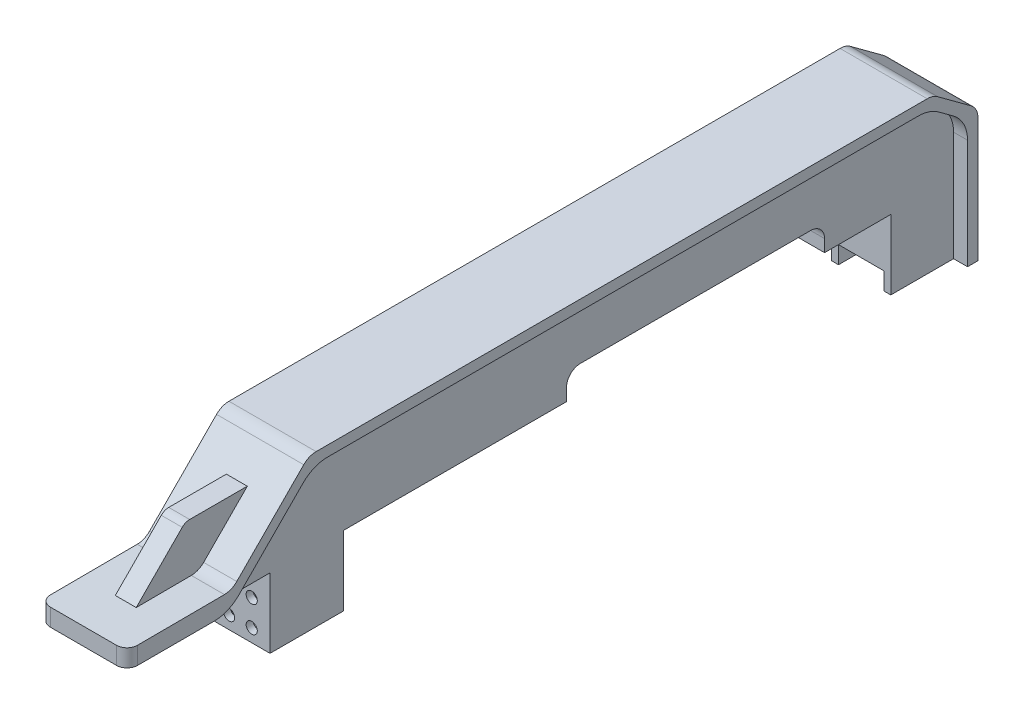
SolidWorks part; units mm, degrees
ref_plane "Front Plane" through (0, 0, 0) normal (0, 0, 1) x (1, 0, 0)
ref_plane "Top Plane" through (0, 0, 0) normal (0, 1, 0) x (1, 0, 0)
ref_plane "Right Plane" through (0, 0, 0) normal (1, 0, 0) x (0, 0, -1)
sketch "Sketch1" plane through (0, 0, 0) normal (1, 0, 0) x (0, 0, -1)
  line L0 (0, 0) -> (-130, 0)
  line L1 (0, 0) -> (74, 0) construction
  line L2 (0, 0) -> (0, 7.5)
  line L3 (0, 7.5) -> (74, 7.5)
  line L4 (74, 7.5) -> (74, 0)
  line L5 (74, 0) -> (114, 0)
  line L6 (-130, 0) -> (-130, 5)
  line L7 (-130, 5) -> (-100.0004, 5.1483)
  line L8 (-100.0004, 5.1483) -> (-77.8685, 27.5)
  line L9 (114, 0) -> (114, 18)
  line L10 (114, 18) -> (101.0882, 27.5)
  line L11 (101.0882, 27.5) -> (-77.8685, 27.5)
  dimension "D1" = 130
  dimension "D2" = 74
  dimension "D3" = 7.5
  dimension "D4" = 40
  dimension "D5" = 30
  dimension "D6" = 5
  dimension "D7" = 135
  dimension "D8" = 20
  dimension "D9" = 18
extrude "Boss-Extrude1" add sketch "Sketch1" along normal blind 25
sketch "Sketch4" plane through (25, 0, 0) normal (1, 0, 0) x (0, 0, -1)
  line L11 (-130, 0) -> (0, 0) construction
  line L12 (-130, 0) -> (0, 0) construction
  line L13 (-100.8762, 0) -> (0, 0)
  line L14 (0, 0) -> (111, 0)
  line L15 (74, 0) -> (114, 0) construction
  line L16 (111, 0) -> (111, 3)
  line L22 (-3, 3) -> (-3, 10.5)
  line L23 (-3, 10.5) -> (77, 10.5)
  line L24 (77, 10.5) -> (77, 3)
  line L25 (77, 3) -> (111, 3)
  line L26 (111, 3) -> (111, 16.4828)
  line L27 (111, 16.4828) -> (100.1035, 24.5)
  line L28 (100.1035, 24.5) -> (-76.6172, 24.5)
  line L29 (-76.6172, 24.5) -> (-97.9057, 3)
  line L30 (-97.9057, 3) -> (-3, 3)
  line L35 (111, 3) -> (111, 16.4828)
  line L36 (111, 16.4828) -> (100.1035, 24.5)
  line L37 (100.1035, 24.5) -> (-76.6172, 24.5)
  line L38 (-76.6172, 24.5) -> (-100.8762, 0)
  dimension "D1" = 3
extrude "Cut-Extrude1" cut sketch "Sketch4" against normal blind 4
ref_plane "Plane1" through (12.5, 0, 0) normal (1, 0, 0) x (0, 0, -1)
mirror "Mirror2" about plane through (12.5, 0, 0) normal (1, 0, 0) of "Cut-Extrude1"
fillet "Fillet1" radius 4 2 edges at (12.5, 7.5, -74) (12.5, 7.5, 0)
fillet "Fillet2" radius 10 8 edges at (23, 16.4828, -111) (23, 24.5, -100.1035) (2, 16.4828, -111) (2, 24.5, -100.1035) (2, 24.5, 76.6172) (23, 24.5, 76.6172) (2, 0, 100.8762) (23, 0, 100.8762)
fillet "Fillet3" radius 5 4 edges at (12.5, 18, -114) (12.5, 27.5, -101.0882) (12.5, 27.5, 77.8685) (12.5, 5.1483, 100.0004)
fillet "Fillet4" radius 3 2 edges at (0, 2.5, 130) (25, 2.5, 130)
sketch "Sketch5" plane through (12.5, 0, 0) normal (1, 0, 0) x (0, 0, -1)
  line L0 (-117.866, 5.06) -> (-103.7939, 19.2718)
  line L1 (-102.0714, 5.138) -> (-127, 5.0148) construction
  line L2 (-79.3359, 26.018) -> (-98.5432, 6.62) construction
  line L3 (-103.7939, 19.2718) -> (-72.6053, 19.2718)
  line L4 (-117.866, 5.06) -> (-95.866, 5.06)
  line L5 (-79.552, 21.536) -> (-97.9414, 2.964) construction
  line L6 (-72.6053, 19.2718) -> (-95.866, 5.06)
  dimension "D1" = 22
  dimension "D2" = 20
extrude "Boss-Extrude2" add sketch "Sketch5" along normal blind 3 and the other way blind 3
fillet "Fillet5" radius 3 1 edges at (12.5, 19.2718, 103.7939)
sketch "Sketch6" plane through (0, 0, 0) normal (0, -1, 0) x (1, 0, 0)
  line L1 (0, -111) -> (0, -114) construction
  line L2 (0, -111) -> (4, -111)
  line L3 (0, -111) -> (0, -114)
  line L4 (0, -114) -> (25, -114)
  line L5 (25, -111) -> (25, -114)
  line L6 (0, -111) -> (25, -114) construction
  line L7 (0, -114) -> (25, -111) construction
  line L8 (4, -111) -> (0, -111) construction
  line L9 (25, -114) -> (0, -114) construction
  line L10 (4, -74) -> (4, -111) construction
  line L11 (4, -111) -> (21, -111) construction
  line L12 (4, -111) -> (4, -93)
  line L13 (4, -93) -> (21, -93)
  line L14 (21, -111) -> (21, -93)
  line L15 (4, -111) -> (21, -93) construction
  line L16 (4, -93) -> (21, -111) construction
  line L17 (21, -74) -> (21, -111) construction
  line L18 (4, -111) -> (21, -111) construction
  line L19 (21, -111) -> (25, -111)
  line L21 (19, -95) -> (6, -95)
  line L22 (19, -95) -> (19, -109)
  line L23 (19, -109) -> (6, -109)
  line L24 (6, -95) -> (6, -109)
  line L25 (19, -95) -> (6, -109) construction
  line L26 (19, -109) -> (6, -95) construction
  point P6 (12.5, -112.5)
  point P16 (12.5, -102)
  point P21 (12.5, -102)
  dimension "D1" = 18
  dimension "D2" = 2
  dimension "D3" = 2
extrude "Boss-Extrude3" add sketch "Sketch6" along normal blind 20
sketch "Sketch7" plane through (0, -20, 0) normal (0, -1, 0) x (1, 0, 0)
  line L0 (19, -109) -> (19, -95) construction
  line L1 (19, -95) -> (6, -95)
  line L2 (19, -95) -> (19, -93)
  line L3 (19, -93) -> (6, -93)
  line L4 (6, -95) -> (6, -93)
  line L5 (19, -95) -> (6, -93) construction
  line L6 (19, -93) -> (6, -95) construction
  line L7 (19, -95) -> (6, -95) construction
  line L8 (21, -93) -> (4, -93) construction
  line L9 (6, -95) -> (6, -109) construction
  point P4 (12.5, -94)
sketch "Sketch8" plane through (0, 0, 0) normal (0, -1, 0) x (1, 0, 0)
  line L5 (21, 85) -> (21, 130) construction
  line L6 (21, 105.0473) -> (21, 0) construction
  line L8 (22, 130) -> (3, 130) construction
  line L9 (4, 105.0473) -> (4, 0) construction
  line L10 (21, 85) -> (4, 85)
  line L11 (21, 85) -> (21, 64)
  line L12 (21, 64) -> (19, 64)
  line L13 (4, 85) -> (4, 64)
  line L14 (21, 85) -> (4, 64) construction
  line L15 (21, 64) -> (4, 85) construction
  line L16 (19, 64) -> (6, 64) construction
  line L17 (6, 64) -> (19, 64) construction
  line L18 (6, 64) -> (6, 83)
  line L19 (6, 83) -> (19, 83)
  line L20 (19, 64) -> (19, 83)
  line L21 (6, 64) -> (19, 83) construction
  line L22 (6, 83) -> (19, 64) construction
  line L23 (6, 64) -> (4, 64)
  point P9 (12.5, 74.5)
  point P16 (12.5, 73.5)
  dimension "D1" = 45
  dimension "D2" = 21
  dimension "D3" = 2
  dimension "D4" = 2
  dimension "D5" = 2
extrude "Boss-Extrude4" add sketch "Sketch8" along normal blind 20
sketch "Sketch9" plane through (0, 0, 0) normal (0, -1, 0) x (1, 0, 0)
  line L0 (6, 64) -> (6, 83) construction
  line L1 (6, 64) -> (19, 64)
  line L2 (6, 64) -> (6, 66)
  line L3 (6, 66) -> (19, 66)
  line L4 (19, 64) -> (19, 66)
  line L5 (6, 64) -> (19, 66) construction
  line L6 (6, 66) -> (19, 64) construction
  line L7 (19, 83) -> (19, 64) construction
  point P4 (12.5, 65)
  dimension "D1" = 2
extrude "Boss-Extrude5" add sketch "Sketch9" along normal blind 8
extrude "Cut-Extrude2" cut sketch "Sketch7" against normal blind 5 contours L3 L4 L1 L2
sketch "Sketch11" plane through (0, 0, -114) normal (0, 0, -1) x (-1, 0, 0)
  line L0 (0, -20) -> (0, -12.5) construction
  line L1 (0, -20) -> (-25, -20) construction
  line L2 (0, -20) -> (0, 15.4713) construction
  line L3 (0, -16.25) -> (-25, -16.25) construction
  line L4 (-25, -20) -> (-25, 15.4713) construction
  line L5 (0, -16.25) -> (-9.25, -16.25) construction
  line L6 (-12.5, -20) -> (-12.5, -5) construction
  line L7 (0, -20) -> (0, -16.25)
  line L8 (-25, -20) -> (-25, -12.5) construction
  line L9 (-25, -12.5) -> (0, -12.5) construction
  circle A0 centre (-9.25, -16.25) radius 1.6
  circle A1 centre (-15.75, -16.25) radius 1.6
  circle A2 centre (-15.75, -8.75) radius 1.6
  circle A3 centre (-9.25, -8.75) radius 1.6
  circle A4 centre (-15.75, -16.25) radius 3 construction
  dimension "D2" = 3.2
  dimension "D5" = 6
  dimension "D1" = 9.25
  dimension "D3" = 3.75
  dimension "D4" = 7.5
extrude "Cut-Extrude3" cut sketch "Sketch11" against normal up to surface (19 mm away) contours A1 | A2 | A3 | A0 region at (9.25, -16.25, -114) region at (15.75, -16.25, -114) region at (15.75, -8.75, -114) region at (9.25, -8.75, -114) up to face at (12.5, -7.5, -95)
sketch "Sketch12" plane through (0, 0, 85) normal (0, 0, 1) x (1, 0, 0)
  line L0 (15.75, -8.75) -> (21, -8.75) construction
  line L1 (15.75, -8.75) -> (15.75, -5) construction
  line L3 (12.5, -20) -> (12.5, -5) construction
  line L6 (0, -12.5) -> (25, -12.5) construction
  line L7 (4, -20) -> (21, -20) construction
  line L8 (4, -20) -> (4, 0) construction
  line L9 (21, -20) -> (21, 0) construction
  circle A0 centre (15.75, -16.25) radius 1.6
  circle A1 centre (9.25, -16.25) radius 1.6
  circle A2 centre (9.25, -8.75) radius 1.6
  circle A3 centre (15.75, -8.75) radius 1.6
  circle A4 centre (9.25, -16.25) radius 3 construction
  dimension "D1" = 3.2
  dimension "D2" = 5.25
  dimension "D3" = 3.75
extrude "Cut-Extrude4" cut sketch "Sketch12" against normal up to surface (2 mm away) up to face at (12.5, -10, 83)
sketch "Sketch14" plane through (12.5, 0, 0) normal (1, 0, 0) x (0, 0, -1)
  line L0 (-83, 0) -> (-83, 13.4752)
  line L1 (-66, 0) -> (-66, 4)
  line L2 (-66, 4) -> (-13.3251, 4)
  line L3 (-13.3251, 4) -> (-5.8251, 11.5)
  line L4 (-5.8251, 11.5) -> (87.0794, 11.5)
  line L5 (95, 0) -> (95, 3.5794)
  line L6 (95, 3.5794) -> (87.0794, 11.5)
  line L7 (109, 0) -> (109, 10.0924)
  line L8 (109, -20) -> (109, 0) construction
  line L9 (95, 0) -> (109, 0) construction
  line L10 (109, 10.0924) -> (95.5924, 23.5)
  line L15 (-72.9752, 23.5) -> (-83, 13.4752)
  line L16 (-83, 0) -> (-66, 0)
  line L17 (95, 0) -> (109, 0)
  line L18 (95.5924, 23.5) -> (-72.9752, 23.5)
  line L19 (-64, 0) -> (0, 0) construction
  line L20 (99.447, 27.5) -> (-75.783, 27.5) construction
  line L21 (70, 7.5) -> (4, 7.5) construction
  point P19 (-63.1231, 36.5624)
  point P20 (-83, 13.4752)
  dimension "D1" = 135
  dimension "D2" = 135
  dimension "D3" = 135
  dimension "D4" = 135
  dimension "D5" = 4
  dimension "D6" = 4
  dimension "D7" = 4
extrude "Cut-Extrude5" cut sketch "Sketch14" against normal blind 6.5 and the other way blind 6.5
